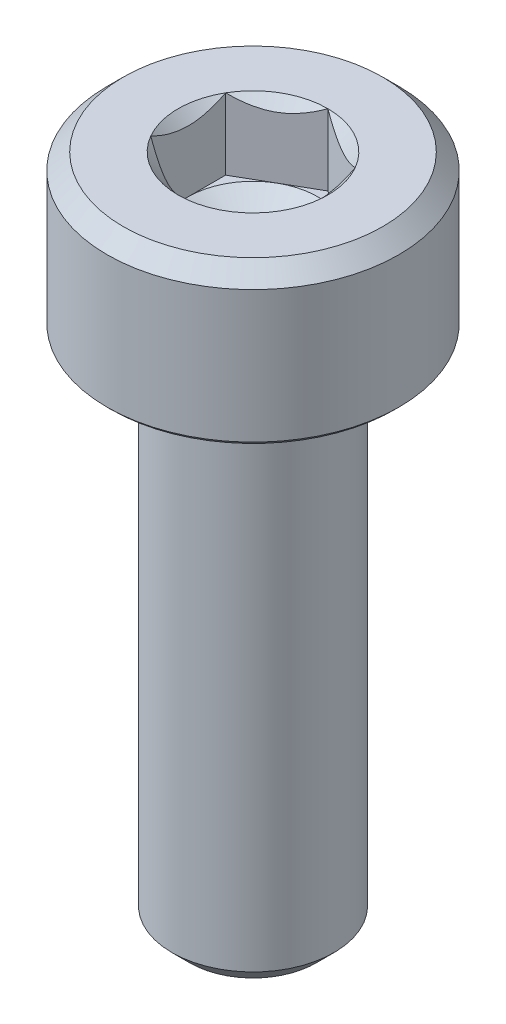
SolidWorks part; units mm, degrees
ref_plane "Front Plane" through (0, 0, 0) normal (0, 0, 1) x (1, 0, 0)
ref_plane "Top Plane" through (0, 0, 0) normal (0, 1, 0) x (1, 0, 0)
ref_plane "Right Plane" through (0, 0, 0) normal (1, 0, 0) x (0, 0, -1)
sketch "Sketch1" plane through (0, 0, 0) normal (0, 0, 1) x (1, 0, 0)
  line L0 (0, 0.6726) -> (1, 1.25)
  line L1 (1, 1.25) -> (1, 2.1953)
  line L2 (1, 2.1953) -> (1.1547, 2.35)
  line L3 (1.1547, 2.35) -> (2, 2.35)
  line L4 (2, 2.35) -> (2.25, 2.1)
  line L5 (2.25, 2.1) -> (2.25, 0.0625)
  line L6 (2.25, 0.0625) -> (2.1875, 0)
  line L7 (2.1875, 0) -> (1.3, 0)
  line L8 (1.3, 0) -> (1.25, -0.51)
  line L9 (1.25, -0.51) -> (1.25, -7.724)
  line L10 (1.25, -7.724) -> (0.974, -8)
  line L11 (0.974, -8) -> (0, -8)
  line L12 (0, -8) -> (0, 0.6726)
  line L13 (0, -8) -> (0, 2.35) construction
revolve "Revolve1" add sketch "Sketch1" angle 360 about L13 reverse direction yes
cosmetic thread "Cosmetic Thread1" parameters "D1"=6.65, "D2"=1.948
ref_plane "Plane1" through (0, 2.35, 0) normal (0, 1, 0) x (1, 0, 0)
sketch "Sketch2" plane through (0, 2.35, 0) normal (0, 1, 0) x (1, 0, 0)
  line L0 (-1, -0.5774) -> (0, -1.1547)
  line L1 (0, -1.1547) -> (1, -0.5774)
  line L2 (1, -0.5774) -> (1, 0.5774)
  line L3 (1, 0.5774) -> (0, 1.1547)
  line L4 (0, 1.1547) -> (-1, 0.5774)
  line L5 (-1, 0.5774) -> (-1, -0.5774)
extrude "Cut-Extrude1" cut sketch "Sketch2" against normal blind 1.1
ref_plane "Plane2" through (0, -8, 0) normal (0, 1, 0) x (1, 0, 0)
ref_plane "ANBAU XY" through (0, 0, 0) normal (0, 1, 0) x (1, 0, 0)
ref_plane "ANBAU XZ" through (0, 0, 0) normal (0, 0, 1) x (1, 0, 0)
ref_plane "ANBAU YZ" through (0, 0, 0) normal (1, 0, 0) x (0, 0, -1)
ref_axis "ANBAU X" through (-80.9, 0, 0) along (1, 0, 0)
ref_axis "ANBAU Y" through (0, 0, 50) along (0, 0, -1)
ref_axis "ANBAU Z" through (0, 50, 0) along (0, -1, 0)
sketch3d "ANBAU"
  point P0 (0, 0, 0)
ref_plane "Schraube XY" through (0, 0, 0) normal (0, 1, 0) x (1, 0, 0)
ref_plane "Schraube XZ" through (0, 0, 0) normal (0, 0, 1) x (1, 0, 0)
ref_plane "Schraube YZ" through (0, 0, 0) normal (1, 0, 0) x (0, 0, -1)
ref_axis "Schraube X" through (-80.9, 0, 0) along (1, 0, 0)
ref_axis "Schraube Y" through (0, 0, 50) along (0, 0, -1)
ref_axis "Schraube Z" through (0, 50, 0) along (0, -1, 0)
sketch3d "Schraube"
  point P0 (0, 0, 0)
ref_plane "insert XY" through (0, 0, 0) normal (0, 1, 0) x (1, 0, 0)
ref_plane "insert XZ" through (0, 0, 0) normal (0, 0, 1) x (1, 0, 0)
ref_plane "insert YZ" through (0, 0, 0) normal (1, 0, 0) x (0, 0, -1)
ref_axis "insert X" through (-80.9, 0, 0) along (1, 0, 0)
ref_axis "insert Y" through (0, 0, 50) along (0, 0, -1)
ref_axis "insert Z" through (0, 50, 0) along (0, -1, 0)
sketch3d "insert"
  point P0 (0, 0, 0)
ref_plane "schrauben_punkt XY" through (0, -8, 0) normal (0, 1, 0) x (1, 0, 0)
ref_plane "schrauben_punkt XZ" through (0, 0, 0) normal (0, 0, 1) x (1, 0, 0)
ref_plane "schrauben_punkt YZ" through (0, 0, 0) normal (1, 0, 0) x (0, 0, -1)
ref_axis "schrauben_punkt X" through (-80.9, -8, 0) along (1, 0, 0)
ref_axis "schrauben_punkt Y" through (0, -8, 50) along (0, 0, -1)
ref_axis "schrauben_punkt Z" through (0, 50, 0) along (0, -1, 0)
sketch3d "schrauben_punkt"
  point P0 (0, -8, 0)
other "Freeze***"
